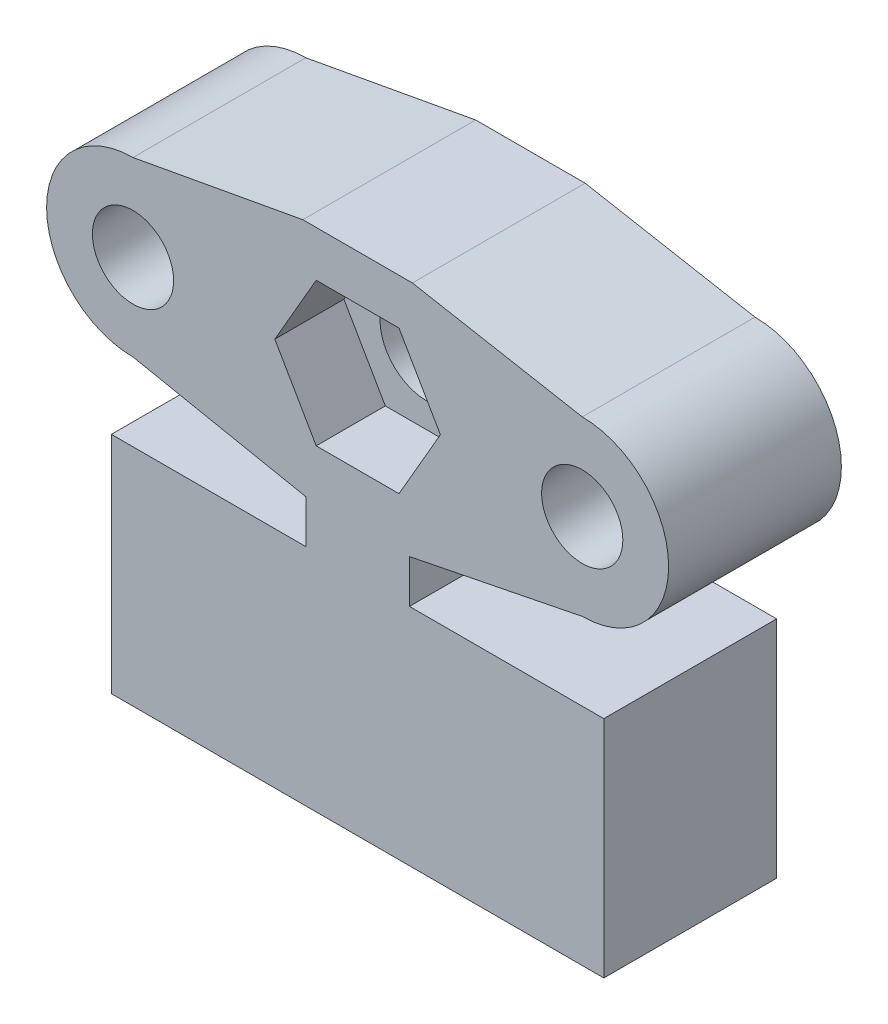
SolidWorks part; units mm, degrees
ref_plane "Plan de face" through (0, 0, 0) normal (0, 0, 1) x (1, 0, 0)
ref_plane "Plan de dessus" through (0, 0, 0) normal (0, 1, 0) x (1, 0, 0)
ref_plane "Plan de droite" through (0, 0, 0) normal (1, 0, 0) x (0, 0, -1)
sketch "Esquisse1" plane through (0, 0, 0) normal (0, 0, 1) x (1, 0, 0)
  line L0 (0, 0) -> (0, 32.7239) construction
  line L1 (-14.25, -6.5) -> (14.25, -6.5)
  line L2 (-14.25, -6.5) -> (-14.25, 6.5)
  line L3 (-14.25, 6.5) -> (-3, 6.5)
  line L4 (14.25, -6.5) -> (14.25, 6.5)
  line L5 (-14.25, -6.5) -> (14.25, 6.5) construction
  line L6 (-14.25, 6.5) -> (14.25, -6.5) construction
  line L7 (-3, 6.5) -> (-3, 9)
  line L8 (3, 6.5) -> (3, 9)
  line L9 (-14.25, 3.5) -> (14.25, 3.5) construction
  line L10 (-2.396, 20.15) -> (0, 16) construction
  line L11 (2.396, 11.85) -> (4.792, 16)
  line L12 (4.792, 16) -> (2.396, 20.15)
  line L13 (2.396, 20.15) -> (-2.396, 20.15)
  line L14 (-2.396, 20.15) -> (-4.792, 16)
  line L15 (-4.792, 16) -> (-2.396, 11.85)
  line L16 (-2.396, 11.85) -> (2.396, 11.85)
  line L17 (0, 16) -> (-13, 16) construction
  line L18 (0, 16) -> (13, 16) construction
  line L19 (3, 9) -> (13, 11)
  line L20 (-3, 9) -> (-13, 11)
  line L21 (-13, 21) -> (-3.1696, 22.7973)
  line L22 (-3.1696, 22.7973) -> (3.1696, 22.7973)
  line L23 (3.1696, 22.7973) -> (13, 21)
  line L24 (3, 6.5) -> (14.25, 6.5)
  circle A0 centre (0, 16) radius 2.7
  circle A1 centre (0, 16) radius 4.15 construction
  circle A2 centre (-13, 16) radius 2.35
  circle A3 centre (13, 16) radius 2.35
  arc A4 (-13, 21) -> (-13, 11) centre (-13, 16) ccw
  arc A5 (13, 11) -> (13, 21) centre (13, 16) ccw
  arc A6 (3.1696, 22.7973) -> (-3.1696, 22.7973) centre (0, 16) ccw
  point P0 (0, 0)
  point P8 (-3, 6.5)
  point P9 (3, 6.5)
  point P16 (0, 3.5)
  point P29 (0, 16)
  point P34 (-3.1696, 22.7973)
  point P37 (3.1696, 22.7973)
  dimension "D7" = 5.4
  dimension "D8" = 8.3
  dimension "D11" = 4.7
  dimension "D12" = 10
  dimension "D13" = 15
  dimension "D1" = 13
  dimension "D2" = 28.5
  dimension "D3" = 6
  dimension "D4" = 2.5
  dimension "D5" = 3
  dimension "D6" = 12.5
  dimension "D9" = 30
  dimension "D10" = 13
  dimension "D14" = 50
extrude "forme principale" add sketch "Esquisse1" along normal blind 10 contours L19 A5 L23 L22 L21 A4 L20 L7 L3 L2 L1 L4 L24 L8 L16 L15 L14 L13 L12 L11 A2 A3 region at (0, 7.211, 0)
extrude "ecrou" add sketch "Esquisse1<5>" along normal blind 6 contours L15 L16 L11 L12 L13 L14 A0 region at (0, 11.9768, 0)
sketch "Esquisse1<5>" plane through (0, 0, 0) normal (0, 0, 1) x (1, 0, 0) same geometry as "Esquisse1"
sketch "Esquisse3" plane through (0, -6.5, 0) normal (0, -1, 0) x (1, 0, 0)
  line L0 (-4.4, 0) -> (-4.4, 10) construction
  line L2 (-9.25, 3) -> (0.45, 3) construction
  line L3 (-14.25, 0) -> (14.25, 0) construction
  line L6 (-14.25, 10) -> (-14.25, 0) construction
  circle A0 centre (-9.25, 3) radius 0.85
  circle A1 centre (0.45, 3) radius 0.85
  point P7 (-4.4, 3)
  dimension "D3" = 1.7
  dimension "D1" = 3
  dimension "D2" = 9.7
  dimension "D4" = 5
extrude "vis" cut sketch "Esquisse3" against normal blind 8
